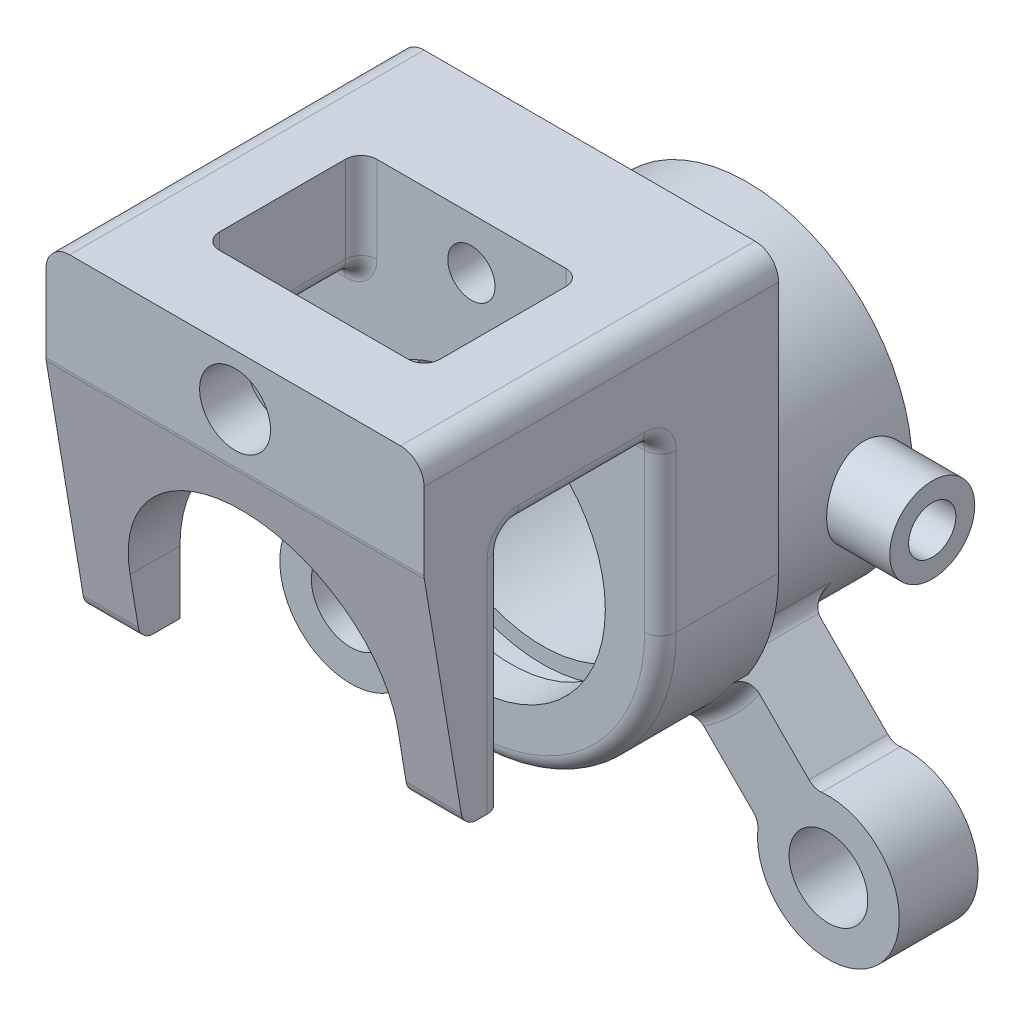
SolidWorks part; units mm, degrees
material "7075-T6 (SN)"
ref_plane "Front Plane" through (0, 0, 0) normal (0, 0, 1) x (1, 0, 0)
ref_plane "Top Plane" through (0, 0, 0) normal (0, 1, 0) x (1, 0, 0)
ref_plane "Right Plane" through (0, 0, 0) normal (1, 0, 0) x (0, 0, -1)
sketch "Sketch1" plane through (0, 0, 0) normal (0, 0, 1) x (1, 0, 0)
  line L0 (0, 120.0929) -> (0, -119.6084) construction
  line L1 (-24, 67.5) -> (-24, 99.5)
  line L2 (-21, 102.5) -> (0, 102.5)
  line L3 (0, 102.5) -> (21, 102.5)
  line L4 (24, 99.5) -> (24, 67.5)
  circle A0 centre (0, 0) radius 85 construction
  circle A1 centre (0, 0) radius 50 construction
  circle A2 centre (0, 0) radius 67.5 construction
  circle A3 centre (0, 67.5) radius 17
  arc A4 (-24, 67.5) -> (24, 67.5) centre (0, 67.5) ccw
  arc A5 (21, 102.5) -> (24, 99.5) centre (21, 99.5) cw
  arc A6 (-24, 99.5) -> (-21, 102.5) centre (-21, 99.5) cw
  point P7 (0, 67.5)
  point P8 (0, 85)
  point P9 (0, 50)
  point P11 (0, 0)
  point P14 (0, 102.5)
  dimension "D1" = 35
  dimension "D2" = 170
  dimension "D3" = 135
  dimension "D4" = 34
  dimension "D5" = 48
  dimension "D7" = 3
  dimension "D6" = 35
extrude "Boss-Extrude1" add sketch "Sketch1" along normal blind 15
sketch "Sketch2" plane through (0, 0, 0) normal (0, 0, -1) x (-1, 0, 0)
  circle A0 centre (0, 67.5) radius 17
  circle A1 centre (0, 67.5) radius 21
  dimension "D1" = 34
  dimension "D2" = 42
extrude "Boss-Extrude2" add sketch "Sketch2" along normal blind 16
sketch "Sketch4" plane through (0, 0, -16) normal (0, 0, -1) x (-1, 0, 0)
  circle A1 centre (0, 67.5) radius 21
  circle A2 centre (0, 67.5) radius 21
  dimension "D1" = 0
extrude "Boss-Extrude3" add sketch "Sketch4" along normal blind 4
sketch "Sketch5" plane through (0, 0, -16) normal (0, 0, 1) x (1, 0, 0)
  circle A0 centre (0, 67.5) radius 17
  circle A1 centre (0, 67.5) radius 14
  dimension "D1" = 34
  dimension "D2" = 28
extrude "Boss-Extrude4" add sketch "Sketch5" along normal blind 3
sketch "Sketch6" plane through (0, 0, 15) normal (0, 0, 1) x (1, 0, 0)
  line L0 (-24, 99.5) -> (-24, 67.5) construction
  line L1 (24, 67.5) -> (24, 99.5) construction
  line L2 (21, 102.5) -> (-21, 102.5) construction
  line L3 (-24, 99.5) -> (-24, 89.5)
  line L4 (24, 89.5) -> (24, 99.5)
  line L5 (21, 102.5) -> (-21, 102.5)
  line L6 (-24, 89.5) -> (24, 89.5)
  arc A0 (24, 99.5) -> (21, 102.5) centre (21, 99.5) ccw construction
  arc A1 (-21, 102.5) -> (-24, 99.5) centre (-21, 99.5) ccw construction
  arc A2 (24, 99.5) -> (21, 102.5) centre (21, 99.5) ccw
  arc A3 (-21, 102.5) -> (-24, 99.5) centre (-21, 99.5) ccw
  point P8 (-24, 89.5)
  dimension "D1" = 10
extrude "Boss-Extrude5" add sketch "Sketch6" along normal blind 30
sketch "Sketch7" plane through (0, 89.5, 0) normal (0, -1, 0) x (1, 0, 0)
  line L0 (24, 45) -> (24, 15) construction
  line L1 (-24, 45) -> (24, 45)
  line L2 (-24, 45) -> (-24, 35)
  line L3 (-24, 35) -> (24, 35)
  line L4 (24, 45) -> (24, 35)
  dimension "D1" = 10
extrude "Boss-Extrude6" add sketch "Sketch7" along normal blind 30
sketch "Sketch8" plane through (0, 0, 15) normal (0, 0, 1) x (1, 0, 0)
  circle A0 centre (0, 67.5) radius 17 construction
  circle A1 centre (0, 67.5) radius 17
extrude "Cut-Extrude1" cut sketch "Sketch8" along normal up to surface (30 mm away) up to face at (0, 87.3738, 45)
sketch "Sketch9" plane through (0, 0, 45) normal (0, 0, 1) x (1, 0, 0)
  line L0 (-17, 67.5) -> (-17, 59.5)
  line L1 (15, 59.5) -> (17, 59.5)
  line L2 (0, 57.2078) -> (0, 66.4973) construction
  line L3 (-15, 59.5) -> (-24, 59.5) construction
  line L4 (-15, 59.5) -> (-17, 59.5)
  line L5 (17, 67.5) -> (17, 59.5)
  arc A0 (15, 59.5) -> (-15, 59.5) centre (0, 67.5) ccw construction
  circle A1 centre (0, 67.5) radius 17 construction
  arc A2 (-17, 67.5) -> (-15, 59.5) centre (0, 67.5) ccw
  arc A3 (17, 67.5) -> (15, 59.5) centre (0, 67.5) cw
extrude "Cut-Extrude2" cut sketch "Sketch9" against normal up to surface (10 mm away) up to face at (0, 73.6667, 35)
sketch "Sketch10" plane through (-24, 0, 0) normal (-1, 0, 0) x (0, 0, 1)
  line L1 (40, 59.5) -> (45, 89.5)
  line L2 (45, 59.5) -> (35, 59.5) construction
  line L3 (45, 99.5) -> (45, 59.5) construction
  line L4 (45, 59.5) -> (40, 59.5)
  line L5 (45, 89.5) -> (45, 59.5)
extrude "Cut-Extrude3" cut sketch "Sketch10" against normal up to surface (48 mm away) up to face at (24, 79, 23.75)
sketch "Sketch11" plane through (0, 102.5, 0) normal (0, 1, 0) x (1, 0, 0)
  line L0 (-14, -35) -> (14, -35)
  line L1 (21, -45) -> (-21, -45) construction
  line L2 (-14, -15) -> (14, -15)
  line L3 (-7, -15) -> (-7, -35) construction
  line L4 (-21, -45) -> (-21, 0) construction
  line L5 (7, -15) -> (7, -35) construction
  line L7 (-14, -15) -> (-14, -35) construction
  line L8 (-14, -15) -> (-14, -35)
  line L9 (14, -15) -> (14, -35) construction
  line L10 (14, -15) -> (14, -35)
  point P12 (-21, -22.5)
  dimension "D1" = 10
  dimension "D2" = 20
  dimension "D3" = 14
  dimension "D4" = 14
  dimension "D5" = 7
  dimension "D6" = 7
extrude "Cut-Extrude4" cut sketch "Sketch11" against normal up to surface (13 mm away) up to face at (0, 89.5, 25)
sketch "Sketch12" plane through (0, 0, 0) normal (0, 0, -1) x (-1, 0, 0)
  line L7 (-28.5643, 46.0067) -> (-17.9577, 56.6133)
  line L12 (-10.8867, 49.5423) -> (-21.4933, 38.9357)
  circle A0 centre (0, 67.5) radius 21 construction
  arc A1 (-17.9577, 56.6133) -> (-10.8867, 49.5423) centre (0, 67.5) ccw
  arc A2 (-28.5643, 46.0067) -> (-21.4933, 38.9357) centre (-30.3203, 37.1797) ccw
  circle A3 centre (-30.3203, 37.1797) radius 5
  dimension "D2" = 18
  dimension "D3" = 10
  dimension "D1" = 10
  dimension "D4" = 15
extrude "Boss-Extrude7" add sketch "Sketch12" along normal blind 10
mirror "Mirror1" about plane through (0, 0, 0) normal (1, 0, 0) of "Boss-Extrude7"
ref_plane "Plane1" through (21, 0, 0) normal (1, 0, 0) x (0, 0, -1)
sketch "Sketch13" plane through (21, 0, 0) normal (1, 0, 0) x (0, 0, -1)
  circle A0 centre (14.5, 67.5) radius 3
  circle A1 centre (14.5, 67.5) radius 5.4
  point P2 (14.5, 67.5)
extrude "Boss-Extrude8" add sketch "Sketch13" along normal blind 8 and the other way blind 3
sketch "Sketch14" plane through (21, 0, 0) normal (1, 0, 0) x (0, 0, -1)
  circle A2 centre (14.5, 67.5) radius 1
extrude "Cut-Extrude5" cut sketch "Sketch14" against normal blind 8
mirror "Mirror2" about plane through (0, 0, 0) normal (1, 0, 0) of "Cut-Extrude5", "Boss-Extrude8"
ref_plane "Plane2" through (0, 0, 10) normal (0, 0, 1) x (1, 0, 0)
sketch "Sketch15" plane through (0, 0, 10) normal (0, 0, 1) x (1, 0, 0)
  circle A0 centre (0, 67.5) radius 17 construction
  circle A1 centre (0, 67.5) radius 17
  circle A2 centre (0, 67.5) radius 19
extrude "Cut-Extrude6" cut sketch "Sketch15" against normal blind 4
sketch "Sketch16" plane through (0, 0, 45) normal (0, 0, 1) x (1, 0, 0)
  circle A0 centre (0, 96) radius 4.5
extrude "Cut-Extrude7" cut sketch "Sketch16" against normal blind 6
sketch "Sketch17" plane through (0, 0, 39) normal (0, 0, 1) x (1, 0, 0)
  circle A0 centre (0, 96) radius 3
extrude "Cut-Extrude8" cut sketch "Sketch17" against normal blind 34
fillet "Fillet1" radius 2 34 edges at (16.9706, 50.5294, 0) (-16.9706, 50.5294, 0) (21.4933, 38.9357, -5) (28.5643, 46.0067, -5) (20.5, 59.5, 40) (-20.5, 59.5, 40) (0, 89.5, 45) (17.9577, 56.6133, -5) (14.8492, 52.6508, -10) (10.8867, 49.5423, -5) (0, 46.5, 0) (-10.8867, 49.5423, -5) (-14.8492, 52.6508, -10) (-17.9577, 56.6133, -5) (-21.4933, 38.9357, -5) (-28.5643, 46.0067, -5) (14, 96, 35) (14, 96, 15) (19, 89.5, 15) (-19, 89.5, 15) (-14, 96, 15) (-14, 96, 35) (-19, 89.5, 35) (19, 89.5, 35) (0, 88.5, 0) (0, 43.5, 15) (-24, 74.5, 35) (-24, 78.5, 15) (24, 74.5, 35) (24, 78.5, 15) (-24, 89.5, 25) (24, 89.5, 25) (14, 89.5, 25) (-14, 89.5, 25)
